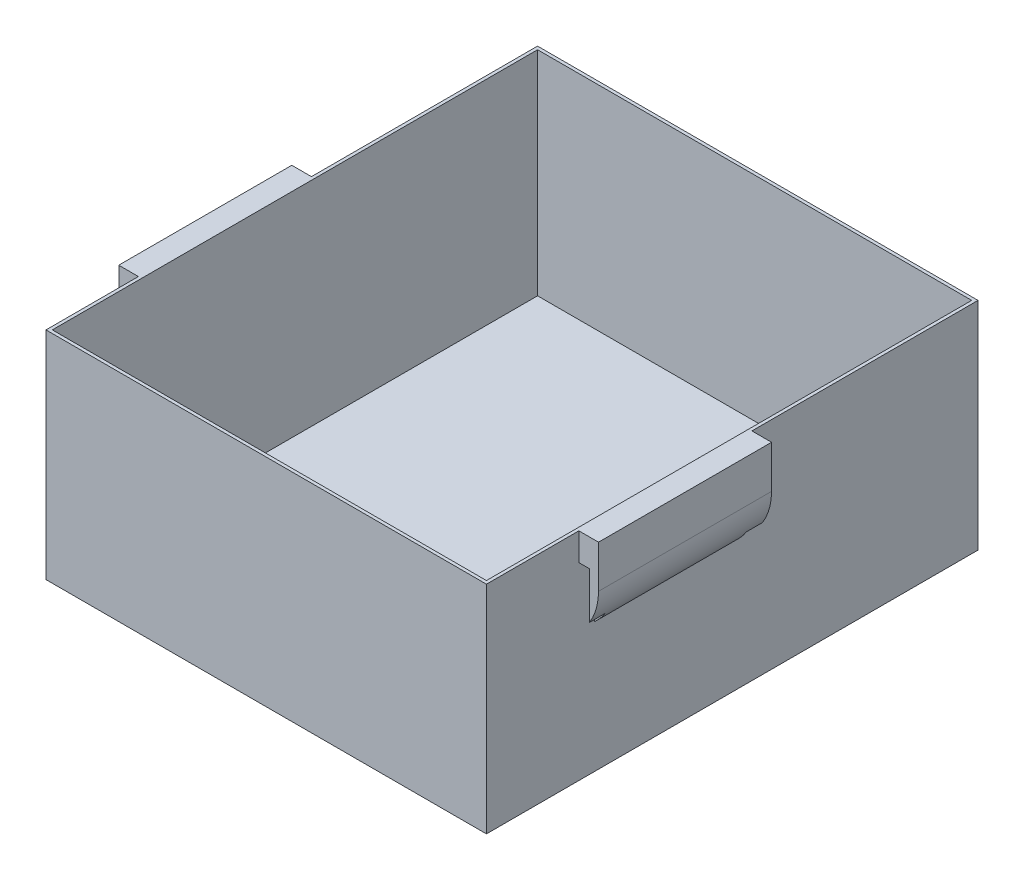
SolidWorks part; units mm, degrees
ref_plane "Front Plane" through (0, 0, 0) normal (0, 0, 1) x (1, 0, 0)
ref_plane "Top Plane" through (0, 0, 0) normal (0, 1, 0) x (1, 0, 0)
ref_plane "Right Plane" through (0, 0, 0) normal (1, 0, 0) x (0, 0, -1)
sketch "Sketch1" plane through (0, 0, 0) normal (0, 1, 0) x (1, 0, 0)
  line L1 (-56, 62.5) -> (56, 62.5)
  line L2 (-56, 62.5) -> (-56, -62.5)
  line L3 (-56, -62.5) -> (56, -62.5)
  line L4 (56, 62.5) -> (56, -62.5)
  line L5 (-56, 62.5) -> (56, -62.5) construction
  line L6 (-56, -62.5) -> (56, 62.5) construction
  point P0 (0, 0)
  dimension "D1" = 125
  dimension "D2" = 112
extrude "Boss-Extrude1" add sketch "Sketch1" along normal blind 55
sketch "Sketch2" plane through (0, 55, 0) normal (0, 1, 0) x (1, 0, 0)
  line L0 (56, -62.5) -> (56, 62.5) construction
  line L1 (-55.2, 61.7) -> (55.2, 61.7)
  line L2 (-55.2, 61.7) -> (-55.2, -61.7)
  line L3 (-55.2, -61.7) -> (55.2, -61.7)
  line L4 (55.2, 61.7) -> (55.2, -61.7)
  line L5 (-55.2, 61.7) -> (55.2, -61.7) construction
  line L6 (-55.2, -61.7) -> (55.2, 61.7) construction
  line L7 (-56, -62.5) -> (56, -62.5) construction
  point P0 (0, 0)
  dimension "D1" = 0.8
  dimension "D2" = 0.8
extrude "Cut-Extrude1" cut sketch "Sketch2" against normal blind 54.2
sketch "Sketch3" plane through (56, 0, 0) normal (1, 0, 0) x (0, 0, -1)
  line L0 (-62.5, 55) -> (62.5, 55) construction
  line L1 (-39, 55) -> (5, 55)
  line L2 (-39, 55) -> (-39, 33)
  line L3 (-39, 33) -> (5, 33)
  line L4 (5, 55) -> (5, 33)
  line L5 (-62.5, 55) -> (-62.5, 0) construction
  dimension "D1" = 22
  dimension "D2" = 44
  dimension "D3" = 23.5
extrude "Boss-Extrude2" add sketch "Sketch3" along normal blind 5
sketch "Sketch4" plane through (0, 0, 39) normal (0, 0, 1) x (1, 0, 0)
  line L1 (56, 33) -> (58.65, 33)
  line L2 (56, 33) -> (56, 48)
  line L3 (56, 48) -> (58.65, 48)
  line L4 (58.65, 33) -> (58.65, 48)
  dimension "D1" = 15
  dimension "D2" = 2.65
extrude "Cut-Extrude2" cut sketch "Sketch4" against normal blind 4
sketch "Sketch6" plane through (0, 0, -5) normal (0, 0, -1) x (-1, 0, 0)
  line L1 (-56, 33) -> (-58.65, 33)
  line L2 (-56, 33) -> (-56, 48)
  line L3 (-56, 48) -> (-58.65, 48)
  line L4 (-58.65, 33) -> (-58.65, 48)
  dimension "D1" = 2.65
  dimension "D2" = 15
extrude "Cut-Extrude3" cut sketch "Sketch6" against normal blind 4
mirror "Mirror5" about plane through (0, 0, 0) normal (1, 0, 0) of "Boss-Extrude2"
mirror "Mirror6" about plane through (0, 0, 0) normal (1, 0, 0) of "Cut-Extrude2"
mirror "Mirror7" about plane through (0, 0, 0) normal (1, 0, 0) of "Cut-Extrude3"
fillet "Fillet1" radius 15 1 edges at (61, 33, 17)
fillet "Fillet2" radius 15 1 edges at (-61, 33, 17)
